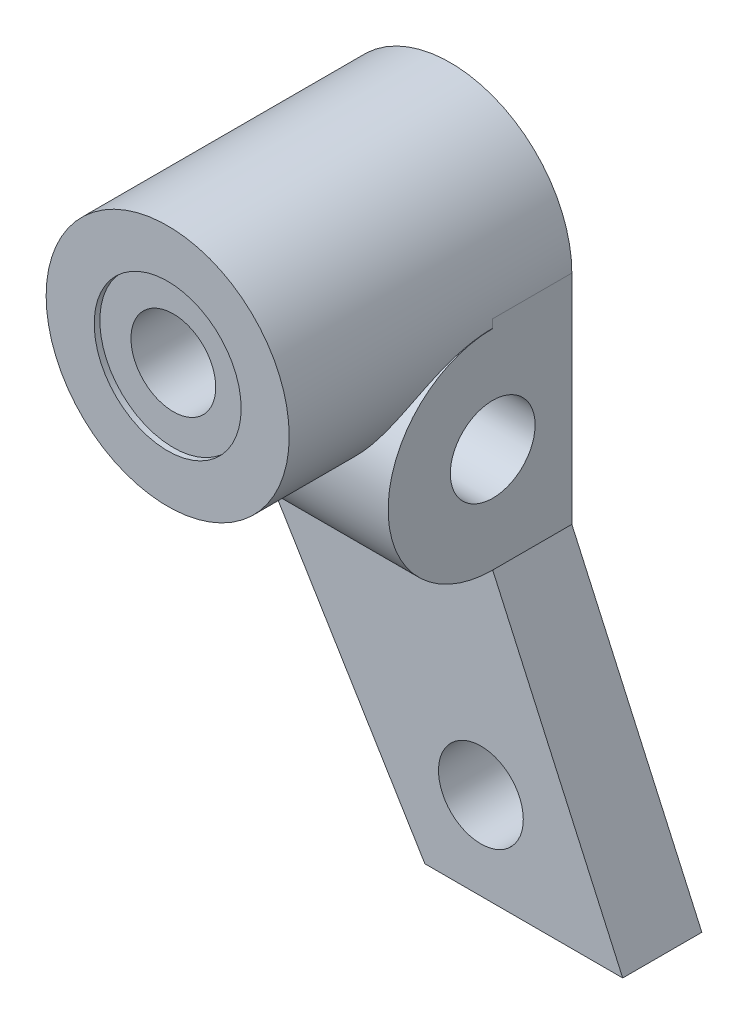
SolidWorks part; units mm, degrees
ref_plane "前视基准面" through (0, 0, 0) normal (0, 0, 1) x (1, 0, 0)
ref_plane "上视基准面" through (0, 0, 0) normal (0, 1, 0) x (1, 0, 0)
ref_plane "右视基准面" through (0, 0, 0) normal (1, 0, 0) x (0, 0, -1)
sketch "草图1" plane through (0, 0, 0) normal (0, 0, 1) x (1, 0, 0)
  line L0 (-4.3, 0) -> (-4.3, -7.7)
  line L1 (-4.3, -7.7) -> (4.3, -7.7)
  line L2 (4.3, -7.7) -> (4.3, 0)
  line L3 (4.3, -7.7) -> (8.9, -17.9)
  line L4 (8.9, -17.9) -> (1.9, -17.9)
  line L5 (1.9, -17.9) -> (-4.3, -7.7)
  circle A0 centre (0, 0) radius 4.3
  circle A1 centre (3.8819, -14.8) radius 1.5
  circle A2 centre (0, 0) radius 1.5
  dimension "D1" = 8.6
  dimension "D6" = 3
  dimension "D9" = 3
  dimension "D2" = 7.7
  dimension "D3" = 10.2
  dimension "D4" = 4.6
  dimension "D5" = 7
  dimension "D7" = 3.1
  dimension "D8" = 3.3
extrude "凸台-拉伸1" add sketch "草图1" along normal blind 2.8 contours A0 | A0 L0 L1 L2 | L5 L4 L3 L1 A1 region at (0, -5.4321, 0) region at (0, 4.1784, 0) region at (2.4834, -12.4136, 0)
sketch "草图2" plane through (4.3, 0, 0) normal (1, 0, 0) x (0, 0, -1)
  line L0 (-2.8, -7.7) -> (-2.8, 0) construction
  line L1 (-2.8, -7.7) -> (0, -7.7) construction
  line L2 (0, -7.7) -> (0, 0) construction
  line L4 (0, -6.4187) -> (0, -1.5813)
  arc A1 (0, -1.5813) -> (0, -6.4187) centre (-2.8, -4) ccw
  dimension "D1" = 7.4
extrude "凸台-拉伸2" add sketch "草图2" against normal blind 9.6
sketch "草图3" plane through (0, 0, 0) normal (0, 0, -1) x (-1, 0, 0)
  arc A0 (4.3, 0) -> (-4.3, 0) centre (0, 0) ccw construction
  circle A1 centre (0, 0) radius 1.5 construction
  circle A2 centre (0, 0) radius 4.3
  circle A3 centre (0, 0) radius 1.5
extrude "凸台-拉伸4" add sketch "草图3" against normal blind 10
sketch "草图4" plane through (0, 0, 10) normal (0, 0, 1) x (1, 0, 0)
  circle A0 centre (0, 0) radius 2.6
  circle A1 centre (0, 0) radius 1.5
  dimension "D1" = 5.2
extrude "切除-拉伸1" cut sketch "草图4" against normal blind 0.2
sketch "草图5" plane through (-5.3, 0, 0) normal (-1, 0, 0) x (0, 0, 1)
  line L0 (0, -6.4187) -> (0, -1.5813) construction
  line L1 (0.8, -5.1547) -> (2.8, -6.3094)
  line L2 (2.8, -6.3094) -> (4.8, -5.1547)
  line L3 (4.8, -5.1547) -> (4.8, -2.8453)
  line L4 (4.8, -2.8453) -> (2.8, -1.6906)
  line L5 (2.8, -1.6906) -> (0.8, -2.8453)
  line L6 (0.8, -2.8453) -> (0.8, -5.1547)
  circle A0 centre (2.8, -4) radius 2 construction
  dimension "D1" = 4
extrude "切除-拉伸2" cut sketch "草图5" against normal blind 7
sketch "草图6" plane through (4.3, 0, 0) normal (1, 0, 0) x (0, 0, -1)
  circle A0 centre (-2.8, -4) radius 1.5
  dimension "D1" = 3
extrude "切除-拉伸3" cut sketch "草图6" against normal through all
sketch "草图7" plane through (0, 0, 2.8) normal (0, 0, 1) x (1, 0, 0)
  line L1 (5.3341, -17.2949) -> (6.7686, -14.7898)
  line L2 (6.7686, -14.7898) -> (5.3164, -12.2949)
  line L3 (5.3164, -12.2949) -> (2.4297, -12.3051)
  line L4 (2.4297, -12.3051) -> (0.9952, -14.8102)
  line L5 (0.9952, -14.8102) -> (2.4474, -17.3051)
  line L6 (2.4474, -17.3051) -> (5.3341, -17.2949)
  circle A0 centre (3.8819, -14.8) radius 2.5 construction
  dimension "D1" = 5
extrude "凸台-拉伸5" [suppressed] add sketch "草图7" along normal blind 2
sketch "草图8" [suppressed] plane through (0, 0, 4.8) normal (0, 0, 1) x (1, 0, 0)
  line L0 (2.4474, -17.3051) -> (5.3164, -12.2949) construction
  line L1 (0.9952, -14.8102) -> (6.7686, -14.7898) construction
  line L2 (2.4297, -12.3051) -> (0.9952, -14.8102) construction
  circle A0 centre (3.8819, -14.8) radius 1.25
  dimension "D1" = 2.5
extrude "凸台-拉伸6" [suppressed] add sketch "草图8" along normal blind 1.2
sketch "草图9" [suppressed] plane through (0, 0, 6) normal (0, 0, 1) x (1, 0, 0)
  line L0 (2.6319, -14.8) -> (5.1319, -14.8) construction
  circle A0 centre (3.8819, -14.8) radius 1.25 construction
ref_plane "基准面1" [suppressed] through (0, -14.8, 0) normal (0, 1, 0) x (1, 0, 0)
sketch "草图10" [suppressed] plane through (0, -14.8, 0) normal (0, 1, 0) x (1, 0, 0)
  line L0 (3.8819, -6) -> (3.8819, -9.9517) construction
  line L1 (2.6319, -6) -> (5.1319, -6) construction
  line L2 (3.8819, -9.4) -> (5.0819, -9.4)
  line L4 (2.6319, -6) -> (5.1319, -6) construction
  line L5 (3.8819, -9.4) -> (3.8819, -6)
  line L6 (3.8819, -6) -> (5.1464, -6)
  arc A0 (5.0819, -9.4) -> (5.1464, -6) centre (3.8819, -7.6766) ccw
  dimension "D1" = 4.2
  dimension "D2" = 1.2
  dimension "D3" = 3.4
revolve "旋转1" [suppressed] add sketch "草图10" angle 360 about L0
sketch "草图13" [suppressed] plane through (0, -14.8, 0) normal (0, 1, 0) x (1, 0, 0)
  line L0 (5.1319, -5.1167) -> (6.7689, -5.0962)
  line L1 (2.6319, -4.8) -> (5.1319, -4.8) construction
  line L2 (6.7689, -3.3) -> (5.1319, -4.8)
  line L3 (5.1319, -6) -> (5.1319, -4.8) construction
  line L4 (5.1319, -4.8) -> (5.1319, -5.1167)
  line L6 (6.7689, -3.3) -> (7.3142, -3.3)
  line L7 (7.3142, -3.3) -> (7.3142, -5.0962)
  line L8 (7.3142, -5.0962) -> (6.7689, -5.0962)
  line L9 (2.6319, -4.8) -> (5.1319, -4.8) construction
  line L10 (3.8819, -4.8) -> (3.8819, -6.3293) construction
  dimension "D1" = 1.5
revolve "切除-旋转1" [suppressed] cut sketch "草图13" angle 360 about L10
sketch "草图14" [suppressed] plane through (0, 0, 2.8) normal (0, 0, -1) x (-1, 0, 0)
  circle A1 centre (-3.8819, -14.8) radius 1.5
  circle A2 centre (-3.8819, -14.8) radius 1.5
  dimension "D1" = 0
extrude "凸台-拉伸7" [suppressed] add sketch "草图14" along normal blind 6
sketch "草图15" [suppressed] plane through (0, 0, -3.2) normal (0, 0, -1) x (-1, 0, 0)
  circle A0 centre (-3.8819, -14.8) radius 1.5
curve "螺旋线/涡状线1" [suppressed] pitch 0.5 height 5 turns 10
sketch "草图16" [suppressed] plane through (0, -14.8, 0) normal (0, 1, 0) x (1, 0, 0)
  line L0 (2.2411, 2.9016) -> (2.2411, 3.4984)
  line L1 (2.2411, 3.4984) -> (2.6168, 3.273)
  line L2 (2.6168, 3.273) -> (2.6168, 3.127)
  line L3 (2.6168, 3.127) -> (2.2411, 2.9016)
  line L4 (2.3819, 3.2) -> (1.9839, 3.2) construction
  dimension "D1" = 0.1461
  dimension "D2" = 0.5969
  dimension "D3" = 0.3757
  dimension "D4" = 2.7651
sweep "切除-扫描1" [suppressed] cut profiles "草图16" path "螺旋线/涡状线1"
